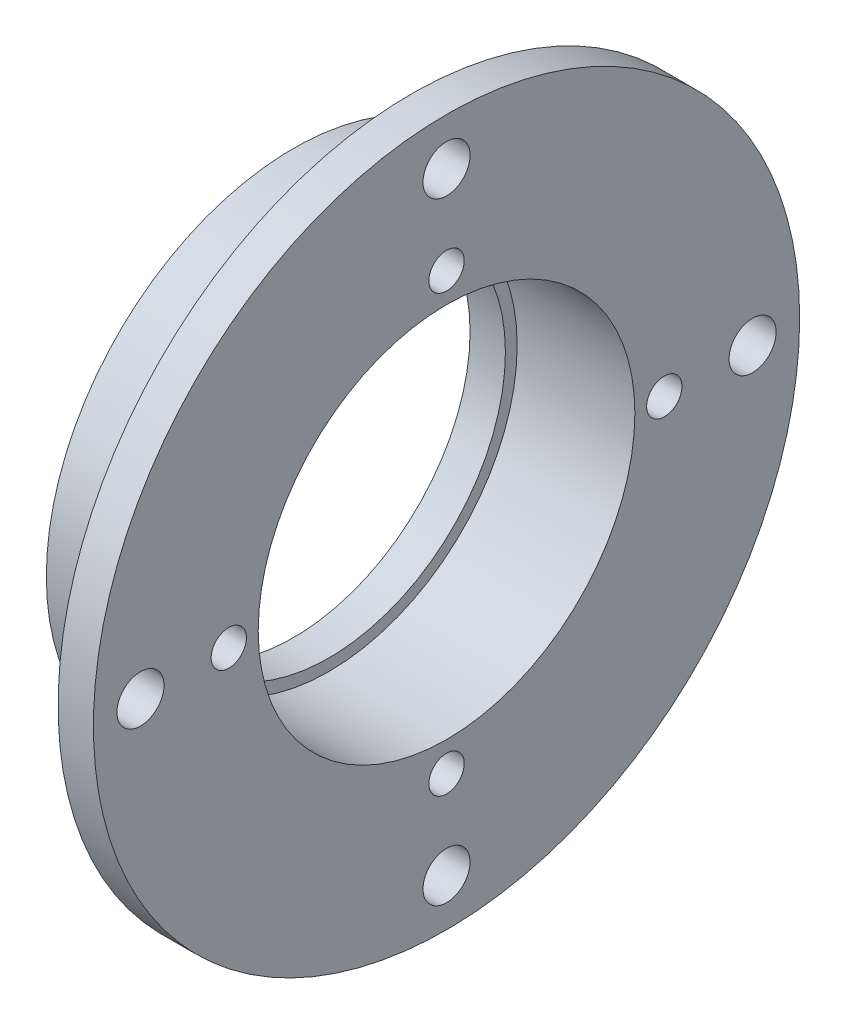
SolidWorks part; units mm, degrees
ref_plane "Front Plane" through (0, 0, 0) normal (0, 0, 1) x (1, 0, 0)
ref_plane "Top Plane" through (0, 0, 0) normal (0, 1, 0) x (1, 0, 0)
ref_plane "Right Plane" through (0, 0, 0) normal (1, 0, 0) x (0, 0, -1)
sketch "Sketch1" plane through (0, 0, 0) normal (1, 0, 0) x (0, 0, -1)
  circle A0 centre (0, 0) radius 21
  dimension "D1" = 42
extrude "Boss-Extrude1" [suppressed] add sketch "Sketch1" along normal blind 7
sketch "Sketch2" [suppressed] plane through (7, 0, 0) normal (1, 0, 0) x (0, 0, -1)
  circle A0 centre (0, 0) radius 30
  dimension "D1" = 60
extrude "Boss-Extrude2" [suppressed] add sketch "Sketch2" along normal blind 3
sketch "Sketch3" [suppressed] plane through (0, 0, 0) normal (-1, 0, 0) x (0, 0, 1)
  circle A0 centre (0, 0) radius 16
  dimension "D1" = 32
extrude "Cut-Extrude1" [suppressed] cut sketch "Sketch3" against normal through all
sketch "Sketch4" [suppressed] plane through (0, 0, 0) normal (-1, 0, 0) x (0, 0, 1)
  circle A0 centre (0, 18.5) radius 1.5
  circle A1 centre (0, 0) radius 18.5 construction
  circle A2 centre (18.5, 0) radius 1.5
  circle A3 centre (0, -18.5) radius 1.5
  circle A4 centre (-18.5, 0) radius 1.5
  point P13 (0, 0)
  dimension "D1" = 3
  dimension "D2" = 37
  dimension "D3" = 4
extrude "Cut-Extrude2" [suppressed] cut sketch "Sketch4" against normal blind 5
sketch "Sketch5" [suppressed] plane through (10, 0, 0) normal (1, 0, 0) x (0, 0, -1)
  circle A0 centre (0, 0) radius 15
  circle A1 centre (0, 0) radius 16 construction
  circle A2 centre (0, 0) radius 16
  dimension "D1" = 30
extrude "Boss-Extrude3" [suppressed] add sketch "Sketch5" against normal blind 3
sketch "Sketch6" [suppressed] plane through (7, 0, 0) normal (-1, 0, 0) x (0, 0, 1)
  circle A0 centre (0, 0) radius 26 construction
  circle A1 centre (0, 26) radius 2
  circle A2 centre (26, 0) radius 2
  circle A3 centre (0, -26) radius 2
  circle A4 centre (-26, 0) radius 2
  point P14 (0, 0)
  dimension "D1" = 52
  dimension "D2" = 4
  dimension "D3" = 4
extrude "Cut-Extrude3" [suppressed] cut sketch "Sketch6" against normal through all
sketch "Sketch8" plane through (0, 0, 0) normal (1, 0, 0) x (0, 0, -1)
  circle A0 centre (0, 0) radius 21
  circle A1 centre (0, 0) radius 16
  dimension "D1" = 32
  dimension "D2" = 42
extrude "Boss-Extrude4" add sketch "Sketch8" along normal blind 7
sketch "Sketch9" plane through (0, 0, 0) normal (-1, 0, 0) x (0, 0, 1)
  circle A1 centre (0, 0) radius 21 construction
  circle A2 centre (0, 0) radius 21
  circle A3 centre (0, 0) radius 15
  dimension "D1" = 30
extrude "Boss-Extrude5" add sketch "Sketch9" along normal blind 3
sketch "Sketch10" plane through (7, 0, 0) normal (1, 0, 0) x (0, 0, -1)
  circle A0 centre (0, 0) radius 16 construction
  circle A1 centre (0, 0) radius 16
  circle A3 centre (0, 0) radius 30
  dimension "D1" = 60
extrude "Boss-Extrude6" add sketch "Sketch10" along normal blind 3
sketch "Sketch11" plane through (10, 0, 0) normal (1, 0, 0) x (0, 0, -1)
  circle A0 centre (0, 0) radius 18.5 construction
  circle A1 centre (0, 0) radius 26 construction
  circle A2 centre (0, 18.5) radius 1.5
  circle A3 centre (0, 26) radius 2
  circle A4 centre (26, 0) radius 2
  circle A5 centre (18.5, 0) radius 1.5
  circle A6 centre (0, -26) radius 2
  circle A7 centre (0, -18.5) radius 1.5
  circle A8 centre (-26, 0) radius 2
  circle A9 centre (-18.5, 0) radius 1.5
  point P9 (-19.8573, 7.3005)
  point P10 (-19.3567, 12.974)
  point P22 (0, 0)
  point P23 (0, 0)
  dimension "D1" = 3
  dimension "D2" = 4
  dimension "D3" = 37
  dimension "D4" = 52
  dimension "D5" = 4
extrude "Cut-Extrude4" cut sketch "Sketch11" against normal blind 6
